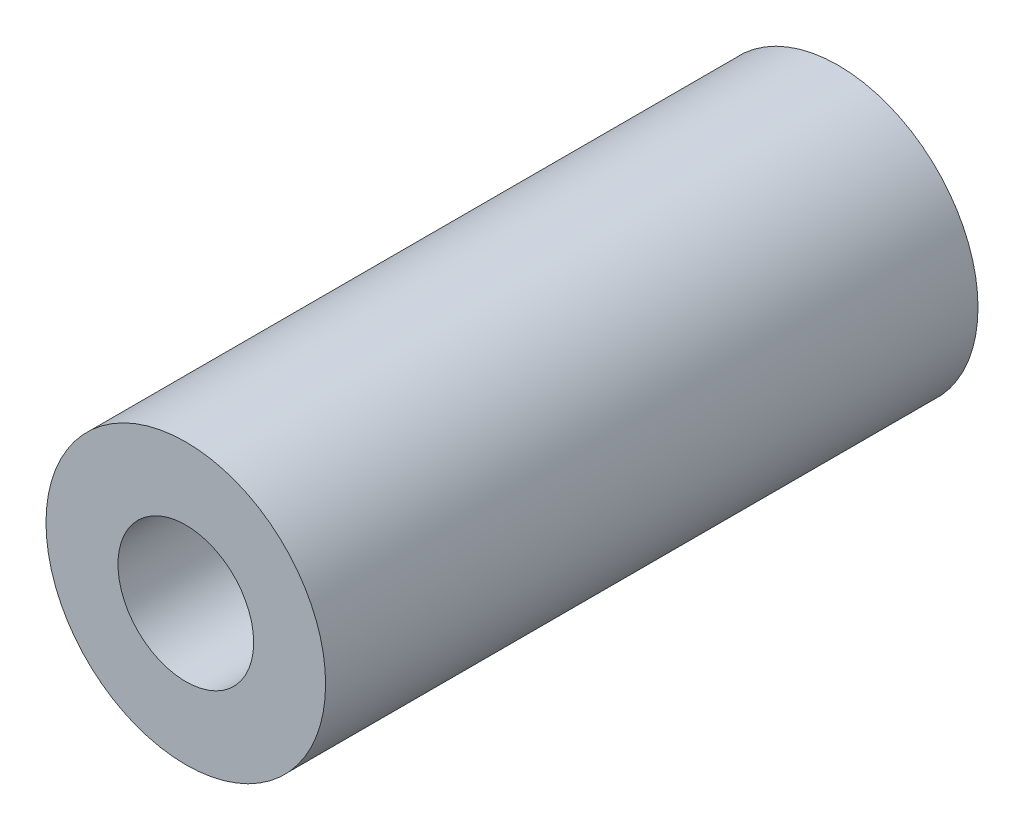
SolidWorks part; units mm, degrees
ref_plane "Front Plane" through (0, 0, 0) normal (0, 0, 1) x (1, 0, 0)
ref_plane "Top Plane" through (0, 0, 0) normal (0, 1, 0) x (1, 0, 0)
ref_plane "Right Plane" through (0, 0, 0) normal (1, 0, 0) x (0, 0, -1)
sketch "Sketch3" plane through (0, 0, 0) normal (0, 0, 1) x (1, 0, 0)
  circle A0 centre (0, 0) radius 1.1557 construction
  circle A1 centre (0, 0) radius 2.3813 construction
  point P6 (0, -1.1557)
  dimension "OD" = 4.7625
  dimension "ID" = 2.3114
sketch "Sketch1" plane through (0, 0, 0) normal (1, 0, 0) x (0, 0, -1)
  line L0 (-5.5562, -1.1557) -> (-5.5562, 1.1557) construction
  line L1 (5.5562, -2.3813) -> (-5.5562, -2.3813) construction
  line L2 (5.5562, -2.3813) -> (5.5562, 2.3813) construction
  line L3 (5.5562, 2.3813) -> (-5.5562, 2.3813) construction
  line L4 (-5.5562, -2.3813) -> (-5.5562, 2.3813) construction
  line L5 (0, 2.3812) -> (0, -2.3812) construction
  line L6 (5.5563, 0) -> (-5.5563, 0) construction
  point P0 (0, 0)
  point P7 (-5.5563, 0)
  dimension "OD" = 4.7625
  dimension "ID" = 2.3114
sketch "Sketch2" plane through (0, 0, 0) normal (0, 0, 1) x (1, 0, 0)
  circle A0 centre (0, 0) radius 2.3812
  circle A1 centre (0, 0) radius 1.1557
extrude "Extrude1" add sketch "Sketch2" along normal up to vertex and the other way up to vertex up to point (0, -2.3813, 5.5562) other way up to point (0, 2.3813, -5.5562)
ref_axis "Center Axis1" through (0, 0, -31.4325) along (0, 0, 1)
ref_plane "Contact Plane1" through (0, 0, -5.5563) normal (0, 0, 1) x (1, 0, 0)
ref_plane "Contact Plane2" through (0, 0, 5.5563) normal (0, 0, 1) x (1, 0, 0)
equation "\"ID@Sketch1\" = \"ID@Sketch3\""
equation "\"OD@Sketch1\" = \"OD@Sketch3\""
